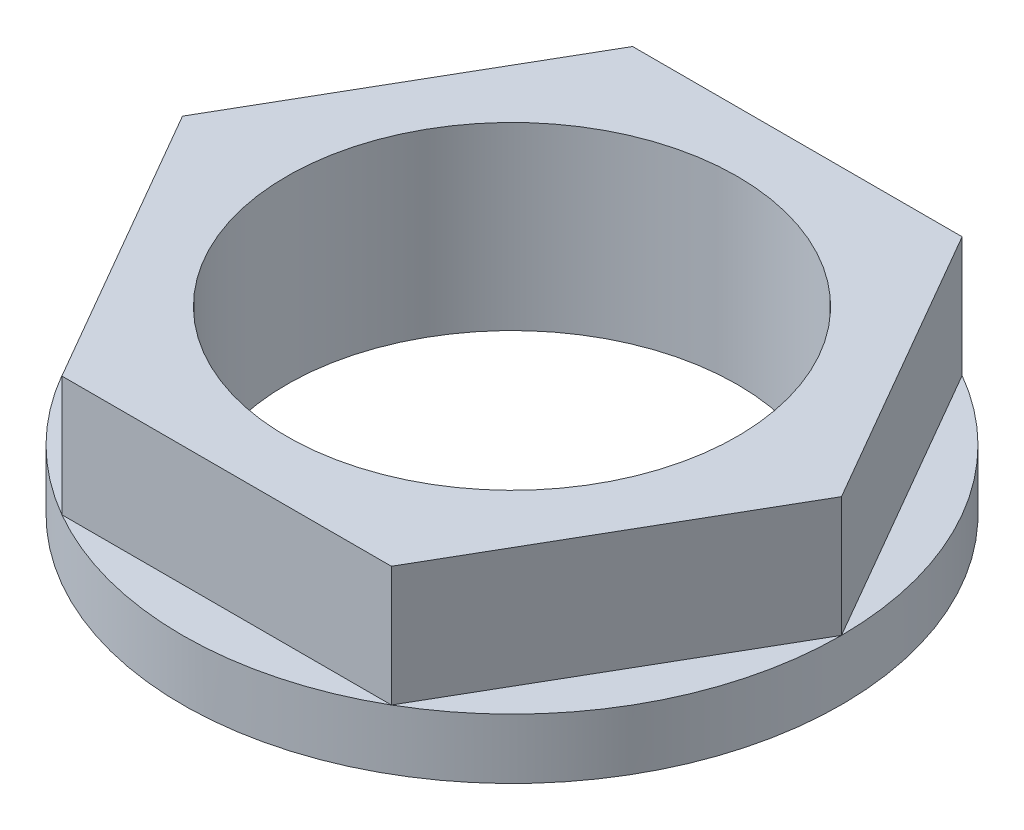
SolidWorks part; units mm, degrees
ref_plane "Спереди" through (0, 0, 0) normal (0, 0, 1) x (1, 0, 0)
ref_plane "Сверху" through (0, 0, 0) normal (0, 1, 0) x (1, 0, 0)
ref_plane "Справа" through (0, 0, 0) normal (1, 0, 0) x (0, 0, -1)
sketch "Эскиз1" plane through (0, 0, 0) normal (0, 1, 0) x (1, 0, 0)
  line L0 (-5.4848, 9.5) -> (5.4848, 9.5)
  line L1 (5.4848, 9.5) -> (10.9697, 0)
  line L2 (10.9697, 0) -> (5.4848, -9.5)
  line L3 (5.4848, -9.5) -> (-5.4848, -9.5)
  line L4 (-5.4848, -9.5) -> (-10.9697, 0)
  line L5 (-10.9697, 0) -> (-5.4848, 9.5)
  dimension "D1" = 9.5
  dimension "D2" = 120
  dimension "D3" = 120
  dimension "D4" = 120
  dimension "D5" = 120
  dimension "D6" = 9.5
  dimension "D7" = 9.5
  dimension "D8" = 9.5
  dimension "D9" = 9.5
  dimension "D10" = 9.5
extrude "Вытянуть1" add sketch "Эскиз1" along normal blind 4
ref_axis "Ось1" through (0, 9.9808, 0) along (0, -1, 0)
sketch "Эскиз3" plane through (0, 0, 0) normal (0, -1, 0) x (1, 0, 0)
  circle A0 centre (0, 0) radius 10.9697
extrude "Вытянуть2" add sketch "Эскиз3" along normal blind 2
sketch "Эскиз4" plane through (0, -2, 0) normal (0, -1, 0) x (1, 0, 0)
  circle A0 centre (0, 0) radius 7.5
  dimension "D1" = 15
extrude "Вырез-Вытянуть1" cut sketch "Эскиз4" against normal through all
